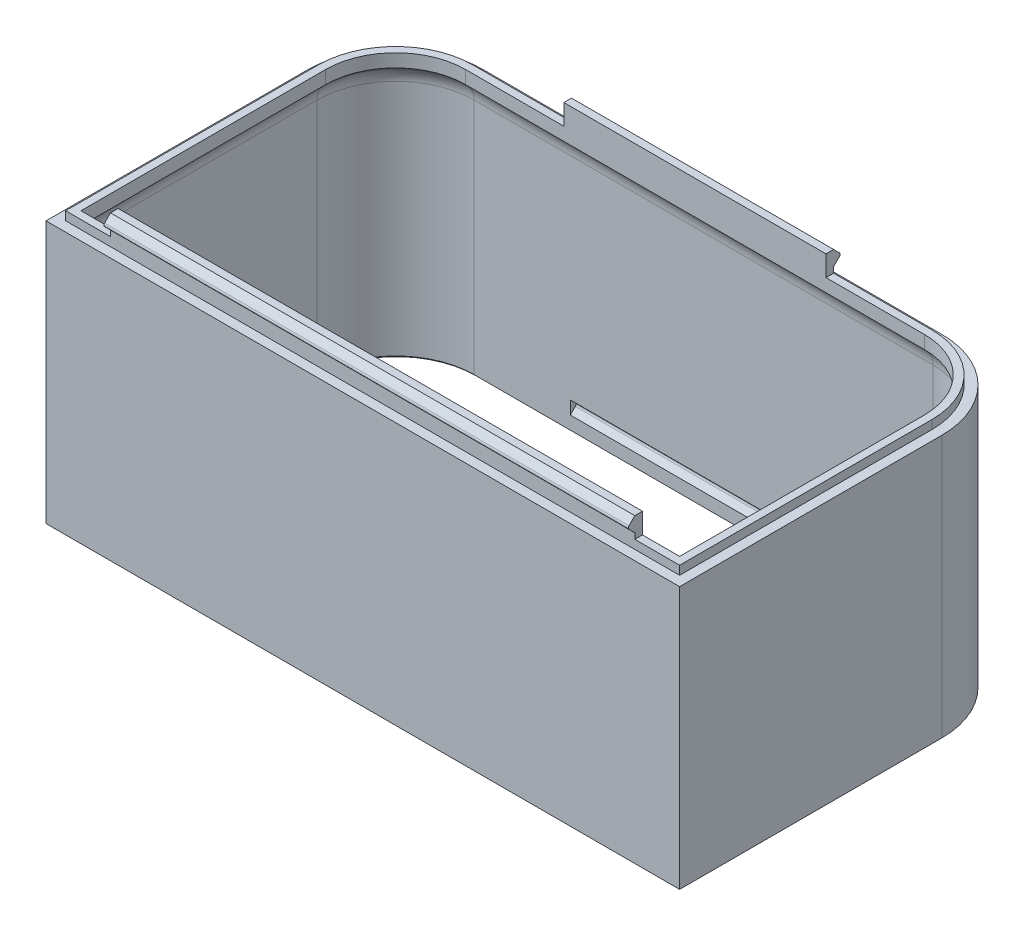
SolidWorks part; units mm, degrees
material "ПК/АБС"
ref_plane "Спереди" through (0, 0, 0) normal (0, 0, 1) x (1, 0, 0)
ref_plane "Сверху" through (0, 0, 0) normal (0, 1, 0) x (1, 0, 0)
ref_plane "Справа" through (0, 0, 0) normal (1, 0, 0) x (0, 0, -1)
sketch "Эскиз1" plane through (0, 0, 0) normal (0, 1, 0) x (1, 0, 0)
  line L0 (-70.5, 2) -> (70.5, 2)
  line L1 (-72.5, 0) -> (72.5, 0)
  line L2 (-72.5, 0) -> (-72.5, 60)
  line L3 (-52.5, 80) -> (52.5, 80)
  line L4 (72.5, 0) -> (72.5, 60)
  line L9 (70.5, 2) -> (70.5, 60)
  line L10 (-52.5, 78) -> (52.5, 78)
  line L11 (-70.5, 2) -> (-70.5, 60)
  arc A0 (72.5, 60) -> (52.5, 80) centre (52.5, 60) ccw
  arc A1 (-52.5, 80) -> (-72.5, 60) centre (-52.5, 60) ccw
  arc A2 (70.5, 60) -> (52.5, 78) centre (52.5, 60) ccw
  arc A3 (-52.5, 78) -> (-70.5, 60) centre (-52.5, 60) ccw
  point P8 (72.5, 80)
  point P11 (-72.5, 80)
  dimension "D3" = 20
  dimension "D1" = 80
  dimension "D2" = 145
  dimension "D4" = 2
extrude "Бобышка-Вытянуть1" add sketch "Эскиз1" along normal blind 60
sketch "Эскиз2" plane through (0, 60, 0) normal (0, 1, 0) x (1, 0, 0)
  line L0 (-68.5, 60) -> (-68.5, 4)
  line L1 (-68.5, 4) -> (68.5, 4)
  line L2 (68.5, 4) -> (68.5, 60)
  line L3 (52.5, 76) -> (-52.5, 76)
  line L4 (-72.5, 60) -> (-72.5, 0)
  line L5 (-72.5, 0) -> (72.5, 0)
  line L6 (72.5, 0) -> (72.5, 60)
  line L7 (52.5, 80) -> (-52.5, 80)
  line L8 (-72.5, 60) -> (-72.5, 0)
  line L9 (-72.5, 0) -> (72.5, 0)
  line L10 (72.5, 0) -> (72.5, 60)
  line L11 (52.5, 80) -> (-52.5, 80)
  arc A0 (68.5, 60) -> (52.5, 76) centre (52.5, 60) ccw
  arc A1 (-52.5, 76) -> (-68.5, 60) centre (-52.5, 60) ccw
  arc A2 (72.5, 60) -> (52.5, 80) centre (52.5, 60) ccw
  arc A3 (-52.5, 80) -> (-72.5, 60) centre (-52.5, 60) ccw
  arc A4 (72.5, 60) -> (52.5, 80) centre (52.5, 60) ccw
  arc A5 (-52.5, 80) -> (-72.5, 60) centre (-52.5, 60) ccw
  dimension "D1" = 0
  dimension "D2" = 4
extrude "Бобышка-Вытянуть2" add sketch "Эскиз2" against normal blind 1
chamfer "Фаска3" distance 2 angle 45 6 edges at (70.5, 59, -31) (65.2279, 59, -72.7279) (0, 59, -78) (-65.2279, 59, -72.7279) (0, 59, -2) (-70.5, 59, -31)
sketch "Эскиз11" plane through (0, 60, 0) normal (0, 1, 0) x (1, 0, 0)
  line L0 (68.5, 4) -> (68.5, 60) construction
  line L1 (-68.5, 4) -> (68.5, 4) construction
  line L2 (-68.5, 60) -> (-68.5, 4) construction
  line L3 (52.5, 76) -> (-52.5, 76) construction
  line L4 (68.5, 4) -> (68.5, 60)
  line L5 (-68.5, 4) -> (68.5, 4)
  line L6 (-68.5, 60) -> (-68.5, 4)
  line L7 (52.5, 76) -> (-52.5, 76)
  line L8 (70.25, 2.25) -> (70.25, 60)
  line L9 (52.5, 77.75) -> (-52.5, 77.75)
  line L10 (-70.25, 60) -> (-70.25, 2.25)
  line L11 (-70.25, 2.25) -> (70.25, 2.25)
  arc A0 (68.5, 60) -> (52.5, 76) centre (52.5, 60) ccw construction
  arc A1 (-52.5, 76) -> (-68.5, 60) centre (-52.5, 60) ccw construction
  arc A2 (68.5, 60) -> (52.5, 76) centre (52.5, 60) ccw
  arc A3 (-52.5, 76) -> (-68.5, 60) centre (-52.5, 60) ccw
  arc A4 (70.25, 60) -> (52.5, 77.75) centre (52.5, 60) ccw
  arc A5 (-52.5, 77.75) -> (-70.25, 60) centre (-52.5, 60) ccw
  dimension "D1" = 1.75
extrude "Бобышка-Вытянуть8" add sketch "Эскиз11" along normal blind 2
sketch "Эскиз12" plane through (0, 0, 0) normal (1, 0, 0) x (0, 0, -1)
  line L0 (76, 59) -> (76, 62) construction
  line L1 (76, 59) -> (76, 62) construction
  line L2 (76, 62) -> (76, 66.7)
  line L3 (76, 66.7) -> (77.75, 66.7)
  line L4 (77.75, 66.7) -> (79.45, 65)
  line L5 (79.45, 65) -> (77.75, 63.3)
  line L6 (77.75, 63.3) -> (77.75, 62)
  line L7 (77.75, 62) -> (76, 62)
  line L9 (80, 60) -> (60, 60) construction
  dimension "D1" = 1.7
  dimension "D2" = 5
extrude "Бобышка-Вытянуть9" add sketch "Эскиз12" along normal mid plane 60
sketch "Эскиз13" plane through (0, 0, 0) normal (1, 0, 0) x (0, 0, -1)
  line L0 (2.25, 62) -> (2.25, 63.3)
  line L1 (2.25, 63.3) -> (0.55, 65)
  line L2 (0.55, 65) -> (2.25, 66.7)
  line L3 (2.25, 66.7) -> (4, 66.7)
  line L4 (4, 66.7) -> (4, 62)
  line L5 (2.25, 62) -> (60, 62) construction
  line L6 (4, 62) -> (2.25, 62)
  line L7 (4, 59) -> (4, 62) construction
  line L8 (4, 59) -> (4, 62) construction
  line L9 (0, 60) -> (60, 60) construction
  dimension "D1" = 5
  dimension "D2" = 1.7
extrude "Бобышка-Вытянуть10" add sketch "Эскиз13" along normal mid plane 120
sketch "Эскиз15" plane through (0, 0, 0) normal (1, 0, 0) x (0, 0, -1)
  line L0 (2, 3.5) -> (2, 6.5)
  line L1 (2, 6.5) -> (0.5, 5)
  line L2 (0.5, 5) -> (2, 3.5)
  line L3 (0, 60) -> (0, 0) construction
  line L4 (0, 0) -> (60, 0) construction
  dimension "D1" = 2
  dimension "D2" = 1.5
  dimension "D3" = 5
extrude "Вырез-Вытянуть2" cut sketch "Эскиз15" against normal mid plane 121
sketch "Эскиз16" plane through (0, 0, 0) normal (1, 0, 0) x (0, 0, -1)
  line L0 (78, 3.5) -> (78, 6.5)
  line L1 (78, 6.5) -> (79.5, 5)
  line L2 (79.5, 5) -> (78, 3.5)
  line L3 (60, 0) -> (80, 0) construction
  dimension "D1" = 2
  dimension "D2" = 1.5
  dimension "D3" = 5
extrude "Вырез-Вытянуть3" cut sketch "Эскиз16" against normal mid plane 61
chamfer "Фаска6" distance 0.5 angle 45 6 edges at (-70.5, 0, -31) (-65.2279, 0, -72.7279) (0, 0, -78) (65.2279, 0, -72.7279) (0, 0, -2) (70.5, 0, -31)
fillet "Скругление3" radius 5 6 edges at (70.5, 57, -31) (65.2279, 57, -72.7279) (0, 57, -78) (-65.2279, 57, -72.7279) (0, 57, -2) (-70.5, 57, -31)
fillet "Скругление4" radius 0.5 2 edges at (0, 5, -0.5) (0, 5, -79.5)
fillet "Скругление5" radius 0.5 2 edges at (0, 65, -79.45) (0, 65, -0.55)
sketch "Эскиз18" plane through (0, 0, 0) normal (0, 0, 1) x (1, 0, 0)
  line L0 (-72.5, 0) -> (72.5, 0) construction
  line L1 (-11, 30) -> (-10, 30)
  line L2 (-11, 30) -> (-11, 0)
  line L3 (-11, 0) -> (-10, 0)
  line L4 (-10, 30) -> (-10, 0)
  line L5 (-10, 30) -> (10, 30) construction
  line L6 (10, 30) -> (11, 30)
  line L7 (10, 30) -> (10, 0)
  line L8 (10, 0) -> (11, 0)
  line L9 (11, 30) -> (11, 0)
  line L10 (0, 0) -> (0, 30) construction
  dimension "D1" = 20
  dimension "D2" = 1
  dimension "D3" = 30
extrude "Вырез-Вытянуть4" [suppressed] cut sketch "Эскиз18" against normal up to surface (2 mm away)
